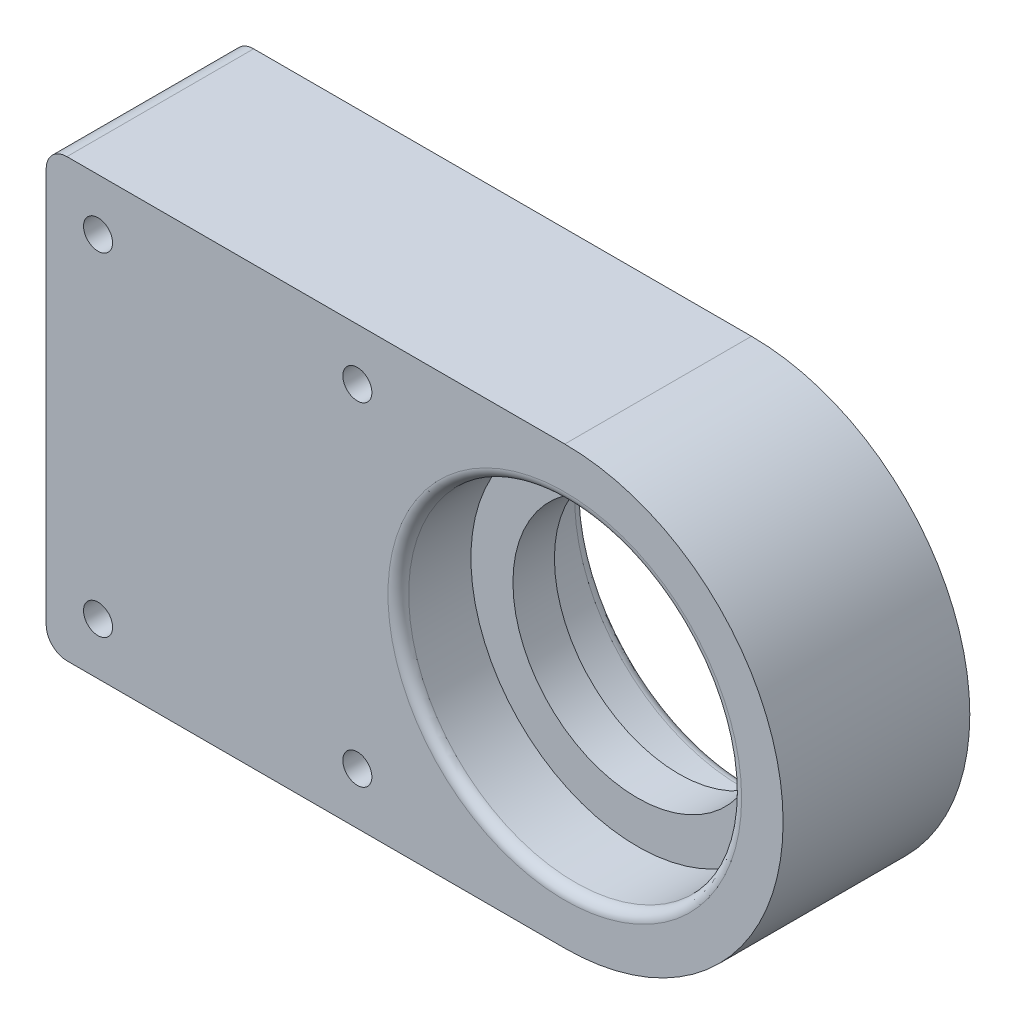
SolidWorks part; units mm, degrees
ref_plane "Front Plane" through (0, 0, 0) normal (0, 0, 1) x (1, 0, 0)
ref_plane "Top Plane" through (0, 0, 0) normal (0, 1, 0) x (1, 0, 0)
ref_plane "Right Plane" through (0, 0, 0) normal (1, 0, 0) x (0, 0, -1)
sketch "Sketch1" plane through (0, 0, 0) normal (0, 0, 1) x (1, 0, 0)
  line L0 (0, 21.05) -> (-50, 21.05)
  line L1 (-50, 21.05) -> (-50, -21.05)
  line L2 (-50, -21.05) -> (0, -21.05)
  circle A0 centre (0, 0) radius 16.05
  arc A1 (0, -21.05) -> (0, 21.05) centre (0, 0) ccw
  dimension "D1" = 32.1
  dimension "D2" = 5
  dimension "D3" = 50
extrude "Boss-Extrude1" add sketch "Sketch1" along normal blind 9 and the other way blind 9
sketch "Sketch2" plane through (0, 0, 0) normal (0, 0, -1) x (-1, 0, 0)
  line L3 (0, -21.05) -> (50, -21.05)
  line L4 (50, -21.05) -> (50, 21.05)
  line L5 (50, 21.05) -> (0, 21.05)
  line L6 (0, -21.05) -> (50, -21.05)
  line L7 (50, -21.05) -> (50, 21.05)
  line L8 (50, 21.05) -> (0, 21.05)
  circle A0 centre (0, 0) radius 12
  arc A1 (0, 21.05) -> (0, -21.05) centre (0, 0) ccw
  arc A2 (0, 21.05) -> (0, -21.05) centre (0, 0) ccw
  dimension "D2" = 24
  dimension "D1" = 0
extrude "Boss-Extrude2" add sketch "Sketch2" against normal offset from surface 7 and the other way offset from surface 7 up to face at (-19.7375, 0, 9) other way up to face at (16.05, 0, -9)
sketch "Sketch3" plane through (0, 0, 9) normal (0, 0, 1) x (1, 0, 0)
  line L0 (0, 21.05) -> (-50, 21.05) construction
  line L1 (-45, 16.05) -> (-20, 16.05) construction
  line L2 (-45, 16.05) -> (-45, -16.05) construction
  line L3 (-45, -16.05) -> (-20, -16.05) construction
  line L4 (-20, 16.05) -> (-20, -16.05) construction
  line L5 (-50, 21.05) -> (-50, -21.05) construction
  line L6 (-50, -21.05) -> (0, -21.05) construction
  circle A0 centre (-45, 16.05) radius 1.4
  circle A1 centre (-20, 16.05) radius 1.4
  circle A2 centre (-20, -16.05) radius 1.4
  circle A3 centre (-45, -16.05) radius 1.4
  dimension "D1" = 5
  dimension "D2" = 5
  dimension "D3" = 5
  dimension "D4" = 25
extrude "Cut-Extrude1" cut sketch "Sketch3" against normal through all
fillet "Fillet1" radius 2 2 edges at (-50, -21.05, 0) (-50, 21.05, 0)
fillet "Fillet2" radius 1 2 edges at (16.05, 0, -9) (16.05, 0, 9)
